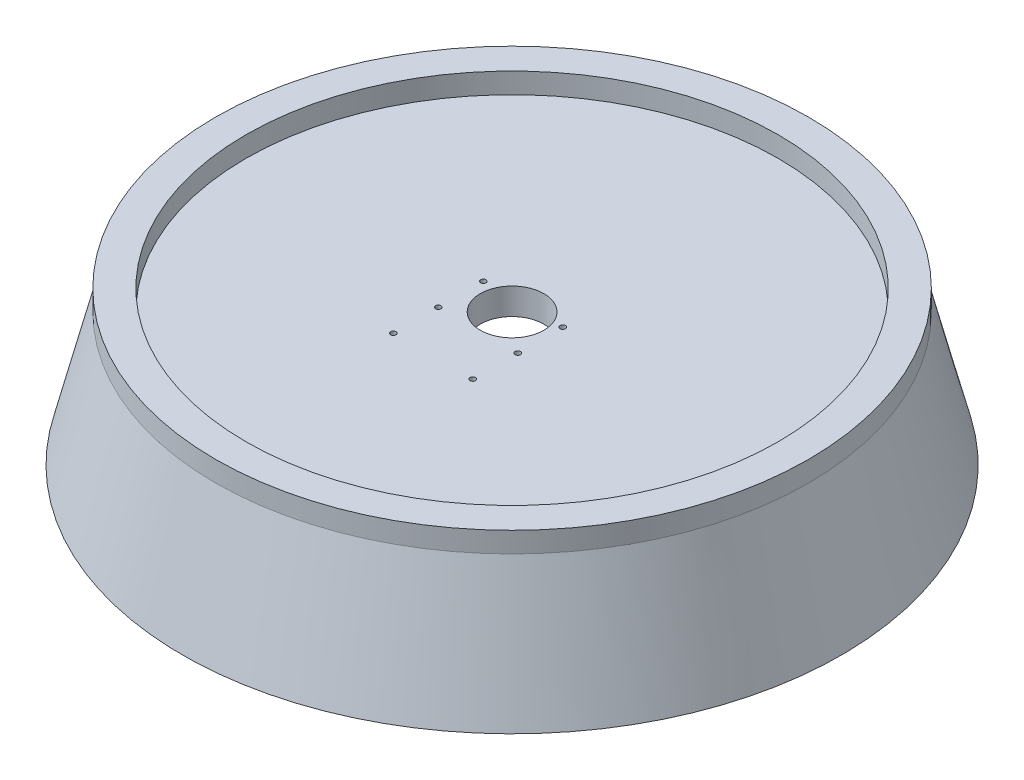
SolidWorks part; units mm, degrees
ref_plane "Front Plane" through (0, 0, 0) normal (0, 0, 1) x (1, 0, 0)
ref_plane "Top Plane" through (0, 0, 0) normal (0, 1, 0) x (1, 0, 0)
ref_plane "Right Plane" through (0, 0, 0) normal (1, 0, 0) x (0, 0, -1)
sketch "Sketch4" plane through (0, 0, 0) normal (0, 0, 1) x (1, 0, 0)
  line L1 (12, 0) -> (12, 50)
  line L2 (12, 50) -> (112, 50)
  line L3 (112, 50) -> (124.5, 0)
  line L4 (12, 40) -> (104.1922, 40)
  line L5 (104.1922, 40) -> (104.1922, 0)
  line L6 (0, 0) -> (0, 40)
  line L7 (104.1922, 0) -> (124.5, 0)
  dimension "D1" = 12
  dimension "D2" = 100
  dimension "D3" = 50
  dimension "D4" = 10
  dimension "D5" = 90
  dimension "D6" = 10
  dimension "D7" = 112.5
ref_axis "Axis4" through (0, 0, 0) along (0, 1, 0)
revolve "Revolve1" add sketch "Sketch4" angle 360 about L6 region at (13.2311, 45, 0)
sketch "Sketch10" plane through (0, 40, 0) normal (0, -1, 0) x (1, 0, 0)
  line L1 (18.25, -12) -> (-18.25, -12)
  line L2 (18.25, -12) -> (18.25, 38.5)
  line L3 (18.25, 38.5) -> (-18.25, 38.5)
  line L4 (-18.25, -12) -> (-18.25, 38.5)
  line L5 (18.25, -12) -> (-18.25, 38.5) construction
  line L6 (18.25, 38.5) -> (-18.25, -12) construction
  circle A0 centre (-15.45, 29.4) radius 1.025
  circle A1 centre (14.55, 29.4) radius 1.025
  circle A2 centre (14.55, 12.4) radius 1.025
  circle A3 centre (14.55, -4.6) radius 1.025
  circle A4 centre (-15.45, 12.4) radius 1.025
  circle A5 centre (-15.45, -4.6) radius 1.025
  point P0 (0, 13.25)
  dimension "D3" = 2.05
  dimension "D1" = 36.5
  dimension "D2" = 50.5
  dimension "D4" = 9.1
  dimension "D5" = 2.8
  dimension "D8" = 17
  dimension "D9" = 30
  dimension "D10" = 12
  dimension "D6" = 2
  dimension "D7" = 3
extrude "Cut-Extrude2" cut sketch "Sketch10" against normal up to surface (10 mm away) contours A2 | A4 | A0 | A1 | A3 | A5 region at (14.55, 40, 12.4) up to face at (0, 50, -112)
sketch "Sketch11" plane through (0, 50, 0) normal (0, 1, 0) x (1, 0, 0)
  circle A0 centre (0, 0) radius 100.5
  circle A1 centre (0, 0) radius 112
  dimension "D1" = 201
  dimension "D2" = 224
extrude "Boss-Extrude1" add sketch "Sketch11" along normal blind 7.75
sketch "Sketch13" plane through (0, 0, 0) normal (0, 0, 1) x (1, 0, 0)
  line L0 (104.1922, 0) -> (84.1922, 0)
  line L1 (-104.1922, 0) -> (104.1922, 0) construction
  line L2 (84.1922, 0) -> (84.1922, 10)
  line L3 (-104.1922, 40) -> (104.1922, 40) construction
  line L4 (54.1922, 40) -> (15.575, 40)
  line L5 (54.1922, 40) -> (104.1922, 40)
  line L6 (104.1922, 40) -> (104.1922, 0)
  arc A0 (84.1922, 10) -> (54.1922, 40) centre (54.1922, 10) ccw
  point P9 (104.1922, 40)
  point P16 (84.1922, 40)
  dimension "D1" = 20
  dimension "D2" = 30
extrude "Boss-Extrude2" add sketch "Sketch13" along normal mid plane 40 contours A0 L2 L0 L6 L5 region at (90.9443, 22.5863, 0)
pattern_circular "CirPattern1" count 5 over 360 about axis through (0, 40, 0) along (0, -1, 0) of "Boss-Extrude2"
